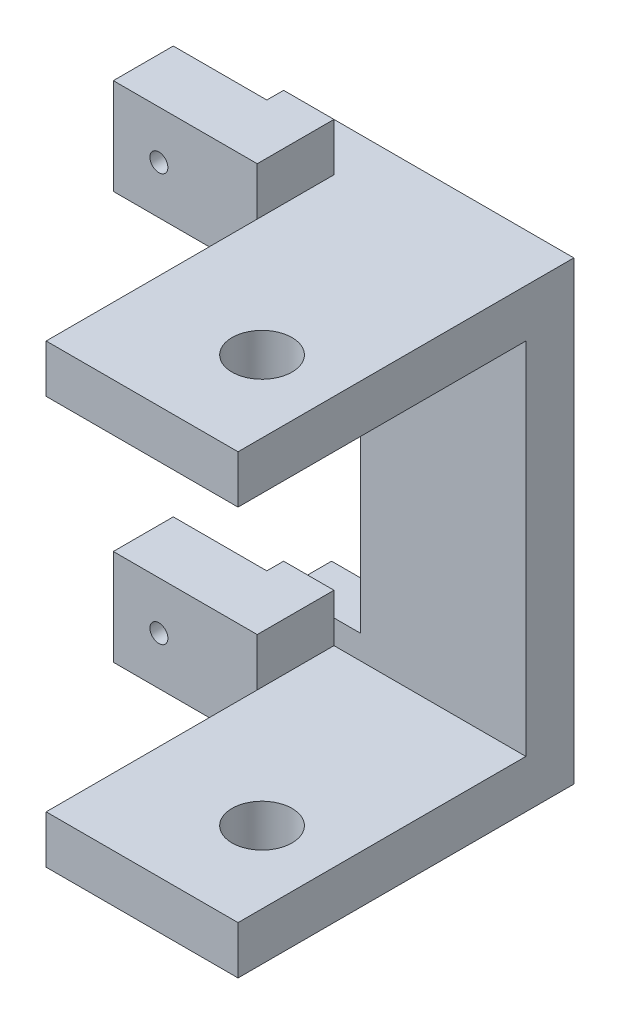
SolidWorks part; units mm, degrees
ref_plane "前视基准面" through (0, 0, 0) normal (0, 0, 1) x (1, 0, 0)
ref_plane "上视基准面" through (0, 0, 0) normal (0, 1, 0) x (1, 0, 0)
ref_plane "右视基准面" through (0, 0, 0) normal (1, 0, 0) x (0, 0, -1)
sketch "草图2" plane through (0, 0, 0) normal (0, 0, 1) x (1, 0, 0)
  line L3 (-5.9, -9.75) -> (6.1, -9.75)
  line L4 (6.1, 9.25) -> (6.1, -9.75)
  line L5 (0, 0) -> (2.4933, 0) construction
  line L6 (0, 0) -> (0, -3.9686) construction
  line L15 (-5.9, 9.25) -> (6.1, 9.25)
  line L20 (-5.9, 9.25) -> (-5.9, 6.75)
  line L21 (-5.9, 6.75) -> (-0.8, 6.75)
  line L26 (-0.8, 6.75) -> (-0.8, -6.75)
  line L28 (-5.9, -6.75) -> (-0.8, -6.75)
  line L29 (-5.9, -6.75) -> (-5.9, -9.75)
  point P0 (0, 0)
  dimension "D1" = 12
  dimension "D2" = 5.1
  dimension "D3" = 19
  dimension "D4" = 3
  dimension "D5" = 13.5
extrude "凸台-拉伸1" add sketch "草图2" along normal blind 2
sketch "草图3" plane through (0, 0, 2) normal (0, 0, 1) x (1, 0, 0)
  line L1 (-1.9, 9.25) -> (6.1, 9.25)
  line L2 (-1.9, 9.25) -> (-1.9, 7.25)
  line L3 (-1.9, 7.25) -> (6.1, 7.25)
  line L4 (6.1, 9.25) -> (6.1, 7.25)
  line L5 (6.1, -9.75) -> (6.1, 9.25) construction
  line L6 (-1.9, -7.75) -> (6.1, -7.75)
  line L8 (-1.9, -9.75) -> (6.1, -9.75)
  line L9 (6.1, -7.75) -> (6.1, -9.75)
  line L10 (-5.9, -9.75) -> (6.1, -9.75) construction
  line L11 (-1.9, -7.75) -> (-1.9, -9.75)
  line L12 (6.1, 9.25) -> (-5.9, 9.25) construction
  dimension "D1" = 2
  dimension "D2" = 2
  dimension "D3" = 8
  dimension "D4" = 8
extrude "凸台-拉伸2" add sketch "草图3" along normal blind 12
sketch "草图10" plane through (0, 0, 2) normal (0, 0, 1) x (1, 0, 0)
  line L9 (-7.9, 11.25) -> (-1.9, 11.25)
  line L10 (-7.9, 11.25) -> (-7.9, 7.25)
  line L11 (-7.9, 7.25) -> (-1.9, 7.25)
  line L12 (-1.9, 11.25) -> (-1.9, 7.25)
  line L13 (-7.9, -5.75) -> (-1.9, -5.75)
  line L14 (-7.9, -5.75) -> (-7.9, -9.75)
  line L15 (-7.9, -9.75) -> (-1.9, -9.75)
  line L16 (-1.9, -5.75) -> (-1.9, -9.75)
  line L17 (-1.9, -7.75) -> (-1.9, -9.75) construction
  line L19 (-1.9, 9.25) -> (-1.9, 7.25) construction
  line L20 (-1.9, 7.25) -> (6.1, 7.25) construction
  line L23 (-5.9, -9.75) -> (-1.9, -9.75) construction
  dimension "D1" = 4
  dimension "D2" = 6
extrude "凸台-拉伸4" add sketch "草图10" along normal blind 3.2
sketch "草图9" plane through (0, 0, 2) normal (0, 0, 1) x (1, 0, 0)
  line L3 (-7.9, 11.25) -> (-7.9, 7.25) construction
  line L4 (-6, 9.25) -> (-6, -7.75) construction
  line L5 (6.1, 9.25) -> (-1.9, 9.25) construction
  line L9 (6.1, -7.75) -> (-1.9, -7.75) construction
  circle A0 centre (-6, 9.25) radius 0.375
  circle A1 centre (-6, -7.75) radius 0.375
  point P10 (-10.8713, 1.8602)
  dimension "D1" = 0.75
  dimension "D2" = 0.75
  dimension "D4" = 1.9
extrude "切除-拉伸2" cut sketch "草图9" against normal up to next from surface starting at face at (-4.3, 9.25, 5.2)
sketch "草图11" plane through (0, -9.75, 0) normal (0, -1, 0) x (1, 0, 0)
  line L0 (-1.9, 14) -> (-1.9, 5.2) construction
  line L3 (-5.9, 0) -> (6.1, 0) construction
  circle A0 centre (3.1, 10) radius 1.25
  dimension "D1" = 2.5
  dimension "D2" = 5
  dimension "D3" = 10
extrude "切除-拉伸3" cut sketch "草图11" against normal through all
sketch "草图12" plane through (0, -9.75, 0) normal (0, -1, 0) x (1, 0, 0)
  line L0 (-7.9, 5.2) -> (-7.9, 2) construction
  line L1 (-7.9, 2.7) -> (-4, 2.7)
  line L2 (-7.9, 2.7) -> (-7.9, 0)
  line L3 (-7.9, 0) -> (-4, 0)
  line L4 (-4, 2.7) -> (-4, 0)
  line L5 (-5.9, 0) -> (6.1, 0) construction
  line L6 (-4.1, 2.6) -> (-7.9, 2.6) construction
  line L7 (-4.1, 0.1) -> (-4.1, 2.6) construction
  dimension "D1" = 0.1
  dimension "D2" = 0.1
extrude "切除-拉伸4" cut sketch "草图12" against normal through all
